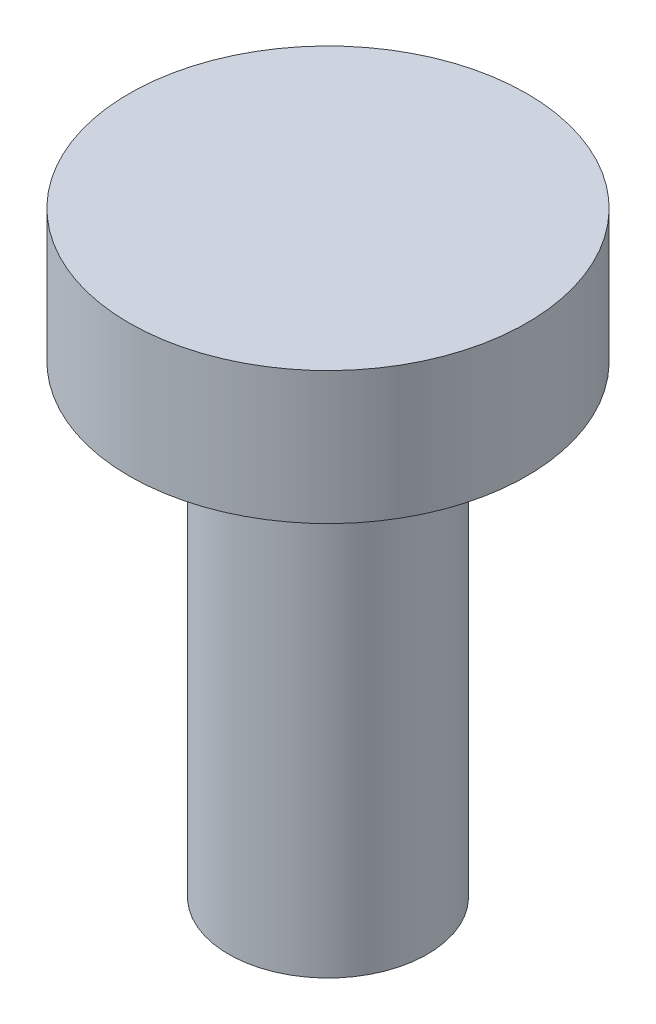
SolidWorks part; units mm, degrees
material "Tin Bearing Bronze"
ref_plane "Спереди" through (0, 0, 0) normal (0, 0, 1) x (1, 0, 0)
ref_plane "Сверху" through (0, 0, 0) normal (0, 1, 0) x (1, 0, 0)
ref_plane "Справа" through (0, 0, 0) normal (1, 0, 0) x (0, 0, -1)
other "Configuration Table"
sketch "Sketch1" plane through (0, 0, 0) normal (0, 0, 1) x (1, 0, 0)
  line L1 (0, 0) -> (1.5, 0)
  line L2 (0, 0) -> (0, 7)
  line L3 (0, 7) -> (1.5, 7)
  line L4 (1.5, 0) -> (1.5, 7)
  line L5 (0, 7) -> (3, 7)
  line L6 (0, 7) -> (0, 9)
  line L7 (0, 9) -> (3, 9)
  line L8 (3, 7) -> (3, 9)
  dimension "D1" = 2
  dimension "D2" = 3
  dimension "D3" = 1.5
  dimension "D4" = 7
revolve "Revolve1" add sketch "Sketch1" angle 360 about L6 region at (0.75, 3.5, 0) region at (1.5, 8, 0)
equation "\"length\"= 7"
equation "\"D4@Sketch1\"=\"length\""
